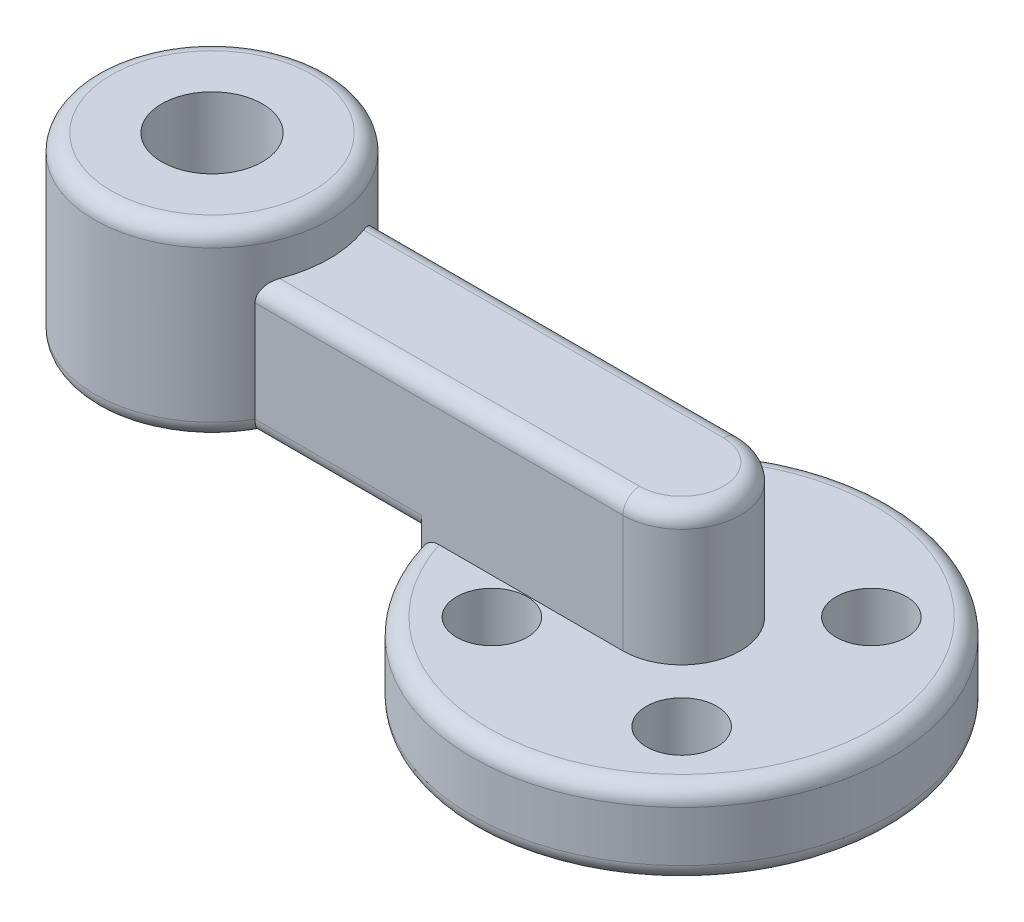
SolidWorks part; units mm, degrees
ref_plane "前视基准面" through (0, 0, 0) normal (0, 0, 1) x (1, 0, 0)
ref_plane "上视基准面" through (0, 0, 0) normal (0, 1, 0) x (1, 0, 0)
ref_plane "右视基准面" through (0, 0, 0) normal (1, 0, 0) x (0, 0, -1)
sketch "草图1" plane through (0, 0, 0) normal (0, 1, 0) x (1, 0, 0)
  circle A0 centre (0, 0) radius 12.5
  dimension "D1" = 25
extrude "凸台-拉伸1" add sketch "草图1" along normal blind 5
sketch "草图2" plane through (0, 5, 0) normal (0, 1, 0) x (1, 0, 0)
  line L0 (0, 0) -> (-28, 0) construction
  line L1 (0, -3.5) -> (-28, -3.5)
  line L2 (0, 3.5) -> (-28, 3.5)
  arc A1 (0, -3.5) -> (0, 3.5) centre (0, 0) ccw
  arc A2 (-28, 3.5) -> (-28, -3.5) centre (-28, 0) ccw
  point P2 (-14, 0)
  dimension "D2" = 3.5
  dimension "D1" = 28
extrude "凸台-拉伸2" add sketch "草图2" along normal blind 8
sketch "草图3" plane through (0, 5, 0) normal (0, 1, 0) x (1, 0, 0)
  line L0 (-5.6569, 5.6569) -> (0, 0) construction
  line L1 (0, 0) -> (0, 8) construction
  circle A0 centre (0, 0) radius 8 construction
  circle A1 centre (-5.6569, 5.6569) radius 1.1
  dimension "D1" = 16
  dimension "D3" = 2.2
  dimension "D2" = 45
extrude "切除-拉伸1" cut sketch "草图3" against normal through all
pattern_circular "阵列(圆周)1" count 4 over 360 about axis through (0, 5, 0) along (0, 1, 0) of "切除-拉伸1"
sketch "草图4" plane through (0, 5, 0) normal (0, 1, 0) x (1, 0, 0)
  circle A0 centre (-5.6569, 5.6569) radius 2.1
  dimension "D1" = 4.2
extrude "切除-拉伸2" cut sketch "草图4" against normal blind 3
pattern_circular "阵列(圆周)2" count 4 over 360 about axis through (0, 5, 0) along (0, -1, 0) of "切除-拉伸2"
sketch "草图5" plane through (0, 13, 0) normal (0, 1, 0) x (1, 0, 0)
  circle A0 centre (-28, 0) radius 7
  dimension "D1" = 14
extrude "凸台-拉伸3" add sketch "草图5" along normal blind 3 and the other way up to surface (8 mm away) other way up to face at (-21, 5, 0)
sketch "草图6" plane through (0, 16, 0) normal (0, 1, 0) x (1, 0, 0)
  circle A0 centre (-28, 0) radius 3
  dimension "D1" = 6
extrude "切除-拉伸3" cut sketch "草图6" against normal through all
sketch "草图7" plane through (0, 5, 0) normal (0, -1, 0) x (1, 0, 0)
  circle A0 centre (-28, 0) radius 5.25
  dimension "D1" = 10.5
extrude "切除-拉伸4" cut sketch "草图7" against normal blind 6
fillet "圆角1" radius 1 8 edges at (-10.9689, 13, -3.5) (3.5, 13, 0) (0, 0, 12.5) (-16.9689, 5, 3.5) (-35, 5, 0) (-16.9689, 5, -3.5) (-10.9689, 13, 3.5) (-28, 16, 7)
fillet "圆角2" radius 1 1 edges at (12.5, 5, 0)
